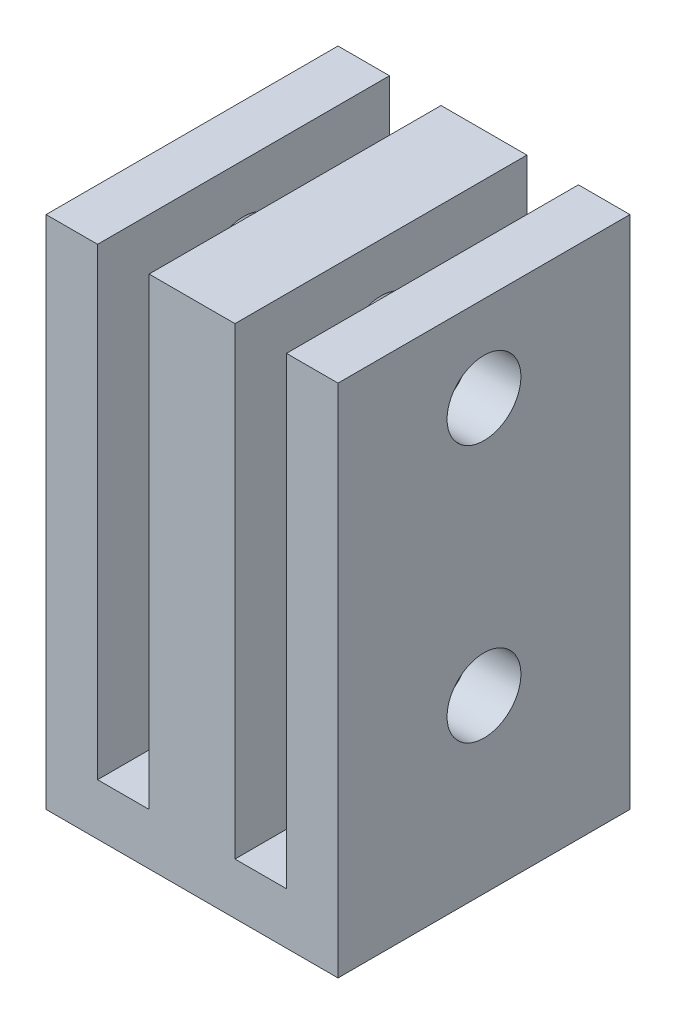
SolidWorks part; units mm, degrees
ref_plane "Front Plane" through (0, 0, 0) normal (0, 0, 1) x (1, 0, 0)
ref_plane "Top Plane" through (0, 0, 0) normal (0, 1, 0) x (1, 0, 0)
ref_plane "Right Plane" through (0, 0, 0) normal (1, 0, 0) x (0, 0, -1)
sketch "Sketch1" plane through (0, 0, 0) normal (0, 1, 0) x (1, 0, 0)
  line L1 (0, 0) -> (17, 0)
  line L2 (0, 0) -> (0, 17)
  line L3 (0, 17) -> (17, 17)
  line L4 (17, 0) -> (17, 17)
  dimension "D1" = 17
extrude "Boss-Extrude1" add sketch "Sketch1" along normal blind 30
sketch "Sketch2" plane through (0, 0, 0) normal (0, 0, 1) x (1, 0, 0)
  line L0 (0, 30) -> (17, 30) construction
  line L1 (3, 30) -> (6, 30)
  line L2 (3, 30) -> (3, 3)
  line L3 (3, 3) -> (6, 3)
  line L4 (6, 30) -> (6, 3)
  line L6 (11, 30) -> (14, 30)
  line L7 (11, 30) -> (11, 3)
  line L8 (11, 3) -> (14, 3)
  line L9 (14, 30) -> (14, 3)
  line L10 (0, 30) -> (0, 0) construction
  line L11 (0, 0) -> (17, 0) construction
  dimension "D1" = 5
  dimension "D2" = 3
  dimension "D3" = 3
  dimension "D4" = 3
extrude "Cut-Extrude1" cut sketch "Sketch2" against normal through all
sketch "Sketch3" plane through (0, 0, 0) normal (-1, 0, 0) x (0, 0, 1)
  line L0 (0, 30) -> (0, 0) construction
  line L2 (-17, 0) -> (0, 0) construction
  circle A0 centre (-8.5, 25) radius 2.15
  circle A1 centre (-8.5, 10) radius 2.15
  point P6 (0, 0)
  dimension "D1" = 4.3
  dimension "D2" = 8.5
  dimension "D3" = 15
  dimension "D4" = 10
extrude "Cut-Extrude2" cut sketch "Sketch3" against normal through all
